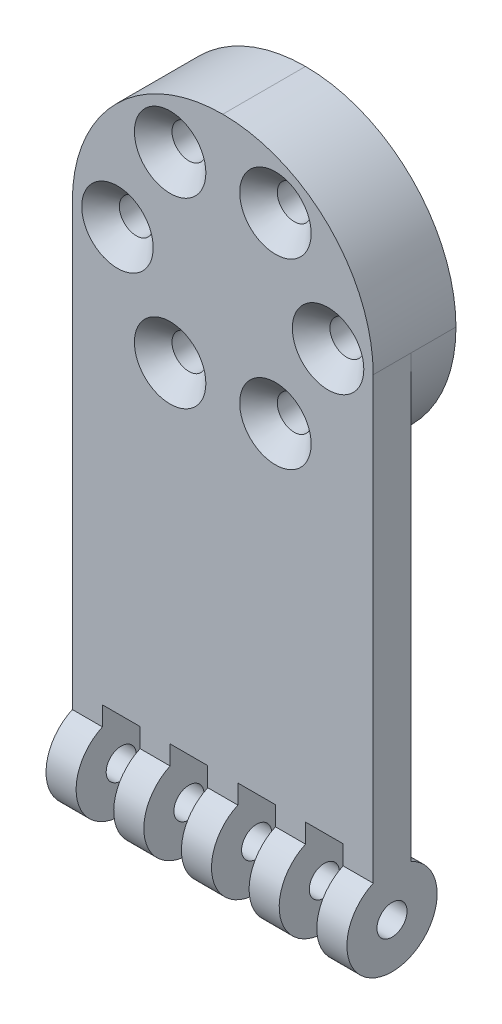
SolidWorks part; units mm, degrees
other "Markup1"
sketch "Sketch13" plane through (20, -53, 11) normal (0.0614, -0.6805, 0.7302) x (0.9699, -0.1321, -0.2046)
ref_plane "Front Plane" through (0, 0, 0) normal (0, 0, 1) x (1, 0, 0)
ref_plane "Top Plane" through (0, 0, 0) normal (0, 1, 0) x (1, 0, 0)
ref_plane "Right Plane" through (0, 0, 0) normal (1, 0, 0) x (0, 0, -1)
sketch "Sketch7" plane through (0, 0, 0) normal (0, 0, 1) x (1, 0, 0)
  line L1 (-20, 20) -> (20, 20)
  line L2 (-20, 20) -> (-20, -20)
  line L3 (-20, -20) -> (20, -20)
  line L4 (20, 20) -> (20, -20)
  line L5 (-20, 20) -> (20, -20) construction
  line L6 (-20, -20) -> (20, 20) construction
  point P0 (0, 0)
extrude "Boss-Extrude1" add sketch "Sketch7" along normal blind 11
sketch "Sketch8" plane through (0, -20, 0) normal (0, -1, 0) x (1, 0, 0)
  line L0 (20, 11) -> (20, 0) construction
  line L1 (-20, 11) -> (20, 11)
  line L2 (-20, 11) -> (-20, 6)
  line L3 (-20, 6) -> (20, 6)
  line L4 (20, 11) -> (20, 6)
  line L5 (0, 6) -> (0, 11) construction
  line L6 (-20, 8.5) -> (20, 8.5) construction
  point P764 (0, 8.5)
extrude "Boss-Extrude2" add sketch "Sketch8" along normal blind 36
sketch "Sketch10" plane through (0, 0, 11) normal (0, 0, 1) x (1, 0, 0)
  circle A0 centre (-7.0001, 12.1244) radius 2.25
  circle A1 centre (6.9999, 12.1244) radius 2.25
  circle A2 centre (13.9999, 0.0001) radius 2.25
  circle A3 centre (6.9999, -12.1243) radius 2.25
  circle A4 centre (-7.0001, -12.1243) radius 2.25
  circle A5 centre (-14.0001, 0.0001) radius 2.25
  point P0 (0, 0)
  point P1 (0.0025, 0.0011)
  dimension "D4" = 4.5
extrude "Cut-Extrude1" cut sketch "Sketch10" against normal blind 25
fillet "Fillet1" radius 20 4 edges at (20, -20, 3) (20, 20, 5.5) (-20, 20, 5.5) (-20, -20, 3)
sketch "Sketch11" plane through (0, -56, 0) normal (0, -1, 0) x (1, 0, 0)
  line L0 (-20, 6) -> (20, 6) construction
  line L1 (-20, 11) -> (-16, 11)
  line L2 (-20, 11) -> (-20, 6)
  line L3 (-20, 6) -> (-16, 6)
  line L4 (-16, 11) -> (-16, 6)
  line L5 (-18, 6) -> (-18, 11) construction
  line L6 (-20, 8.5) -> (-16, 8.5) construction
  point P368 (-18, 8.5)
extrude "Boss-Extrude3" add sketch "Sketch11" along normal blind 9 contours L1 L4 L3 L2
ref_plane "Plane1" through (-16, 0, 0) normal (1, 0, 0) x (0, 0, -1)
sketch "Sketch14" plane through (-16, 0, 0) normal (1, 0, 0) x (0, 0, -1)
  line L0 (-11, -65) -> (-6, -65) construction
  line L1 (-11, 0) -> (-11, -65) construction
  circle A0 centre (-8.5, -64) radius 6
  dimension "D3" = 12
  dimension "D1" = 1
  dimension "D2" = 2.5
extrude "Boss-Extrude4" add sketch "Sketch14" against normal up to vertex (4 mm away) up to point (-20, -65, 11)
pattern_linear "LPattern1" count 5 spacing 9 along (1, 0, 0) of "Boss-Extrude4", "Boss-Extrude3"
sketch "Sketch15" plane through (-20, 0, 0) normal (-1, 0, 0) x (0, 0, 1)
  circle A0 centre (8.5, -64) radius 2
extrude "Cut-Extrude2" cut sketch "Sketch15" against normal through all
chamfer "Chamfer1" distance 2.5 angle 45 6 edges at (-4.7501, 12.1244, 11) (-11.7501, 0.0001, 11) (-4.7501, -12.1243, 11) (9.2499, 12.1244, 11) (16.2499, 0.0001, 11) (9.2499, -12.1243, 11)
